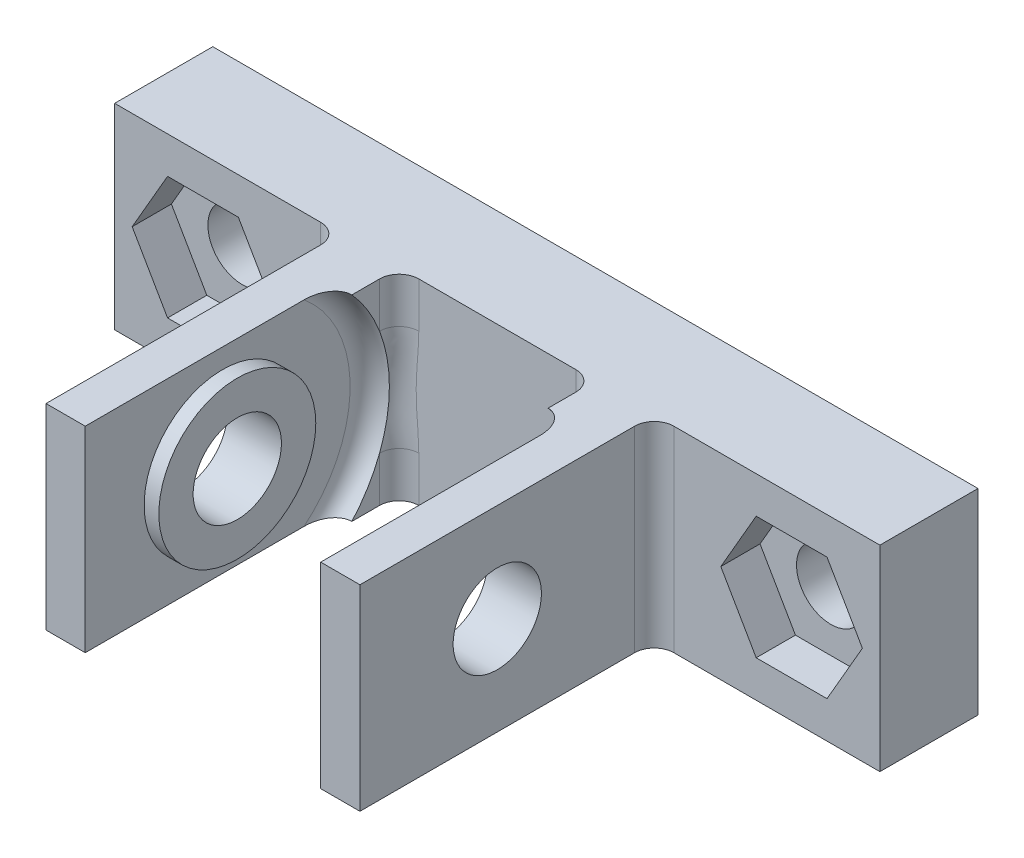
SolidWorks part; units mm, degrees
ref_plane "Front Plane" through (0, 0, 0) normal (0, 0, 1) x (1, 0, 0)
ref_plane "Top Plane" through (0, 0, 0) normal (0, 1, 0) x (1, 0, 0)
ref_plane "Right Plane" through (0, 0, 0) normal (1, 0, 0) x (0, 0, -1)
sketch "Sketch1" plane through (0, 0, 0) normal (0, 1, 0) x (1, 0, 0)
  line L0 (0, 0) -> (0, -20.0709) construction
  line L1 (-8, 0) -> (8, 0)
  line L2 (8, 0) -> (8, -20)
  line L3 (8, -20) -> (5, -20)
  line L4 (5, -20) -> (5, -5)
  line L5 (5, -5) -> (-5, -5)
  line L6 (-5, -20) -> (-5, -5)
  line L7 (-8, -20) -> (-5, -20)
  line L8 (-8, 0) -> (-8, -20)
  line L9 (5, -20) -> (5, -5)
  point P9 (0, -5)
  dimension "D1" = 5
  dimension "D2" = 3
  dimension "D3" = 15
  dimension "D4" = 5
extrude "Boss-Extrude1" add sketch "Sketch1" along normal blind 10 contours L1 L0 L5 L4 L3 L2 | L0 L1 L8 L7 L6 L5 region at (5.3235, 0, 7.7941) region at (-5.3235, 0, 7.7941)
sketch "Sketch2" plane through (8, 0, 0) normal (1, 0, 0) x (0, 0, -1)
  line L0 (-20, 5) -> (0, 5) construction
  line L1 (-20, 10) -> (-20, 0) construction
  line L2 (0, 10) -> (0, 0) construction
  circle A0 centre (-13, 5) radius 2.25
  dimension "D1" = 4.5
  dimension "D2" = 13
extrude "Cut-Extrude1" cut sketch "Sketch2" against normal through all contours A0
sketch "Sketch3" plane through (0, 10, 0) normal (0, 1, 0) x (1, 0, 0)
  line L1 (-19.5, -5) -> (19.5, -5)
  line L2 (0, 0) -> (0, -5) construction
  line L3 (-19.5, 0) -> (19.5, 0)
  line L4 (19.5, -5) -> (19.5, 0)
  line L5 (-8, 0) -> (8, 0) construction
  line L7 (-19.5, -5) -> (-19.5, 0)
  line L8 (5, -5) -> (-5, -5) construction
  dimension "D1" = 19.5
extrude "Boss-Extrude2" add sketch "Sketch3" against normal through all
sketch "Sketch4" plane through (0, 0, 5) normal (0, 0, 1) x (1, 0, 0)
  line L0 (-19.5, 5) -> (-8, 5) construction
  line L1 (-19.5, 0) -> (-19.5, 10) construction
  line L2 (-8, 10) -> (-8, 0) construction
  line L3 (-15, 0) -> (-15, 10) construction
  line L6 (0, 0) -> (0, 10) construction
  line L7 (5, 0) -> (-5, 0) construction
  line L8 (5, 10) -> (-5, 10) construction
  line L9 (15, 0) -> (15, 10) construction
  line L10 (19.5, 5) -> (8, 5) construction
  line L11 (-15, 0) -> (-15, 10) construction
  circle A0 centre (-15, 5) radius 1.75
  circle A1 centre (15, 5) radius 1.75
  dimension "D1" = 3.5
  dimension "D2" = 15
extrude "Cut-Extrude2" cut sketch "Sketch4" against normal through all
sketch "Sketch6" plane through (-5, 0, 0) normal (1, 0, 0) x (0, 0, -1)
  line L0 (-13, 12.5) -> (-20.5, 12.5)
  line L1 (-20.5, 12.5) -> (-20.5, 5)
  line L2 (-20.5, 5) -> (-20.5, -2.5)
  line L3 (-20.5, -2.5) -> (-13, -2.5)
  arc A0 (-13, -2.5) -> (-13, 12.5) centre (-13, 5) ccw
  circle A1 centre (-13, 5) radius 2.25 construction
  dimension "D1" = 15
extrude "Cut-Extrude3" cut sketch "Sketch6" against normal blind 1
sketch "Sketch5" plane through (-6, 0, 0) normal (1, 0, 0) x (0, 0, -1)
  circle A0 centre (-13, 5) radius 4
  circle A1 centre (-13, 5) radius 2.25
  circle A2 centre (-13, 5) radius 2.25 construction
  dimension "D1" = 8
extrude "Boss-Extrude3" add sketch "Sketch5" along normal blind 0.75
mirror "Mirror1" about plane through (0, 0, 0) normal (1, 0, 0) of "Boss-Extrude3", "Cut-Extrude3"
fillet "Fillet1" radius 1 6 edges at (-6, 5, 5.5) (6, 5, 5.5) (5, 5, 5) (-5, 5, 5) (8, 5, 5) (-8, 5, 5)
sketch "Sketch7" plane through (0, 0, 5) normal (0, 0, 1) x (1, 0, 0)
  line L0 (0, 10) -> (0, 0) construction
  line L1 (16.8042, 8.125) -> (13.1958, 8.125)
  line L2 (13.1958, 8.125) -> (11.3916, 5)
  line L3 (11.3916, 5) -> (13.1958, 1.875)
  line L4 (13.1958, 1.875) -> (16.8042, 1.875)
  line L5 (16.8042, 1.875) -> (18.6084, 5)
  line L6 (18.6084, 5) -> (16.8042, 8.125)
  line L7 (4, 10) -> (-4, 10) construction
  line L8 (-18.6084, 5) -> (-16.8042, 8.125)
  line L9 (-16.8042, 1.875) -> (-18.6084, 5)
  line L10 (-13.1958, 1.875) -> (-16.8042, 1.875)
  line L11 (-11.3916, 5) -> (-13.1958, 1.875)
  line L12 (-13.1958, 8.125) -> (-11.3916, 5)
  line L13 (-16.8042, 8.125) -> (-13.1958, 8.125)
  line L14 (18.6084, 5) -> (16.8042, 8.125)
  circle A0 centre (15, 5) radius 3.125 construction
  circle A1 centre (-15, 5) radius 3.125 construction
  circle M5 centre (15, 5) radius 1.75
  dimension "D1" = 6.25
extrude "Cut-Extrude4" cut sketch "Sketch7" against normal blind 2 contours L13 L8 L9 L10 L11 L12 | L5 L6 L1 L2 L3 L4 M5 | M5 region at (17.6236, 6.5148, 5) region at (-15, 5, 5) region at (15, 5, 5)
equation "\"X-ROD-SPACING\"=45"
equation "\"Y-ROD-SPACING\"=75"
equation "\"Z-ROD-SPACING\"=17.5"
equation "\"Y-BED-OFFSET\"=2"
equation "\"Y-BED-ROD-INSET\"=3.5"
equation "\"Y-BED-SCREW-SPACING\"=209"
equation "\"Y-BED-SCREW-CUTOUT-SLOT-HEIGHT\"=2"
equation "\"T-SLOT-NUT-FILLET-RADIUS\"=0.5"
equation "\"T-SLOT-SCREW-SHAFT-RADIUS\"=1.55"
equation "\"T-SLOT-SCREW-SHAFT-CUTOUT-LENGTH\"=11.0"
equation "\"T-SLOT-NUT-DEPTH\"=3.5"
equation "\"T-SLOT-NUT-WIDTH\"=2.85"
equation "\"T-SLOT-NUT-END-DISTANCE\"=8"
equation "\"ACRYLIC-THICKNESS\"=10"
equation "\"ACRYLIC-THICKNESS2\"=4.5"
equation "\"ACRYLIC-TAB-CUTOUT-SIZE\"=\"ACRYLIC-THICKNESS\"+\"ACRYLIC-TAB-TOLERANCE\"*2"
equation "\"ACRYLIC-TAB-TOLERANCE\"=-.05"
equation "\"KERF\"=0.05"
equation "\"ACRYLIC-THICKNESS-TAB-CUTOUT-WIDTH\"=\"ACRYLIC-THICKNESS\"-\"KERF\"*2"
equation "\"ACRYLIC-THICKNESS-TAB-CUTOUT-HEIGHT\"=\"ACRYLIC-TAB-WIDTH\"-\"KERF\"*4"
equation "\"ACRYLIC-THICKNESS2-TAB-CUTOUT-WIDTH\"=\"ACRYLIC-THICKNESS2\"-\"KERF\"*2"
equation "\"ACRYLIC-THICKNESS2-TAB-CUTOUT-HEIGHT\"=\"ACRYLIC-TAB-WIDTH\"-\"KERF\"*4"
equation "\"ACRYLIC-TAB-WIDTH\"=\"ACRYLIC-THICKNESS\""
equation "\"ACRYLIC-M3-HOLE\"=2.9"
equation "\"SMOOTHROD-CAP-SCREW-DISTANCE\"=20"
equation "\"FRAME-WIDTH-INNER\"=370"
equation "\"NEMA17-HOLE-SPACING\"=31"
equation "\"NEMA17-CENTRAL-CUTOUT\"=22.5"
equation "\"Z-BRACKET-REACH\"=55"
equation "\"Z-ROD-INSET\"=16"
equation "\"TOP-BRACKET-SPACING\"=40"
equation "\"SMOOTHROD-X-LENGTH\"=350"
equation "\"SMOOTHROD-Y-LENGTH\"=350"
equation "\"SMOOTHROD-Z-LENGTH\"=350"
equation "\"SMOOTHROD-TIGHTENING-HEADROOM\"=.25"
equation "\"LEADSCREW-Z-LENGTH\"=300"
equation "\"SCREW-LENGTH-FRAME\"=\"ACRYLIC-THICKNESS\" + 10"
equation "\"SCREW-LENGTH-MOTOR\"=\"ACRYLIC-THICKNESS\" + 5"
equation "\"SCREW-LENGTH-EXTRUDER\"=28"
equation "\"SCREW-HEAD-RADIUS\"=6"
equation "\"PRINTED-M3-HOLE\"=3.5"
equation "\"PRINTED-X-SMOOTHROD-DIAMETER\"=8.4"
equation "\"PRINTED-X-SMOOTHROD-CUTOUT\"=10"
equation "\"PRINTED-X-BASE-HEIGHT\"=10"
equation "\"PRINTED-LM8UU-CUTOUT-SIZE\"=15.5"
equation "\"PRINTED-LM8UU-CUTOUT-LENGTH\"=24.5"
equation "\"PRINTED-X-IDLER-HEIGHT\"=16"
equation "\"PRINTED-M3-NUT-AF\"=6.25"
equation "\"PSU-MOUNTING-WIDTH\"=95"
equation "\"PSU-MOUNTING-HEIGHT\"=177"
equation "\"Y-BELT-TO-ROD-DISTANCE\"=20"
equation "\"SPOOL-HOLDER-ROD-SPACING\"=150"
equation "\"ACRYLIC-X-CARRIAGE-WIDTH\"=55"
equation "\"ACRYLIC-X-CARRIAGE-HEIGHT\"=75"
equation "\"ACRYLIC-X-CARRIAGE-LM8UU-CUTOUT-WIDTH\"=24.25"
equation "\"ACRYLIC-X-CARRIAGE-LM8UU-CUTOUT-HEIGHT\"=11.0"
equation "\"ACRYLIC-X-CARRIAGE-SCREW-SPACING-X\"=15"
equation "\"ACRYLIC-X-CARRIAGE-SCREW-SPACING-Y\"=33"
equation "\"ACRYLIC-X-CARRIAGE-CENTER-TAB-SPACING\"=14"
equation "\"ACRYLIC-X-CARRIAGE-EXTRUDER-OFFSET\"=26"
equation "\"ACRYLIC-X-CARRIAGE-EXTRUDER-ANGLE\"=90"
equation "\"ACRYLIC-X-CARRIAGE-EXTRUDER-SHELF-DEPTH\"=\"ACRYLIC-X-CARRIAGE-EXTRUDER-OFFSET\" + 28"
equation "\"ACRYLIC-X-CARRIAGE-EXTRUDER-BRACE-SPACING\"=23"
equation "\"ACRYLIC-X-CARRIAGE-EXTRUDER-BRACE-TAB-OFFSET\"=20"
equation "\"ACRYLIC-X-CARRIAGE-EXTRUDER-BRACE-HEIGHT\"=35"
equation "\"ACRYLIC-X-CARRIAGE-EXTRUDER-BRACE-SCREW-SPACING\"=22"
equation "\"ACRYLIC-X-CARRIAGE-DUAL-WIDTH-MULTIPLIER\"=1.65"
equation "\"ACRYLIC-X-CARRIAGE-DUAL-HOTEND-SPACING\"=42"
equation "\"ACRYLIC-X-CARRIAGE-DUAL-WIDTH\"=75"
equation "\"ACRYLIC-X-CARRIAGE-DUAL-FAN-OFFSET\"=52"
equation "\"ACRYLIC-X-CARRIAGE-DUAL-FAN-HEIGHT\"=20"
equation "\"ACRYLIC-X-CARRIAGE-DUAL-HOTEND-SEPARATION\"=36"
equation "\"ACRYLIC-X-CARRIAGE-DUAL-MOUNT-PLATE-DEPTH\"=75"
equation "\"ACRYLIC-X-CARRIAGE-DUAL-MOUNT-BRACE-WIDTH\"=33"
equation "\"ACRYLIC-X-CARRIAGE-DUAL-MOUNT-SCREW-WIDTH\"=40"
equation "\"BLOWER-FAN-WIDTH\"=15"
equation "\"D1@Sketch7\"=\"PRINTED-M3-NUT-AF\""
